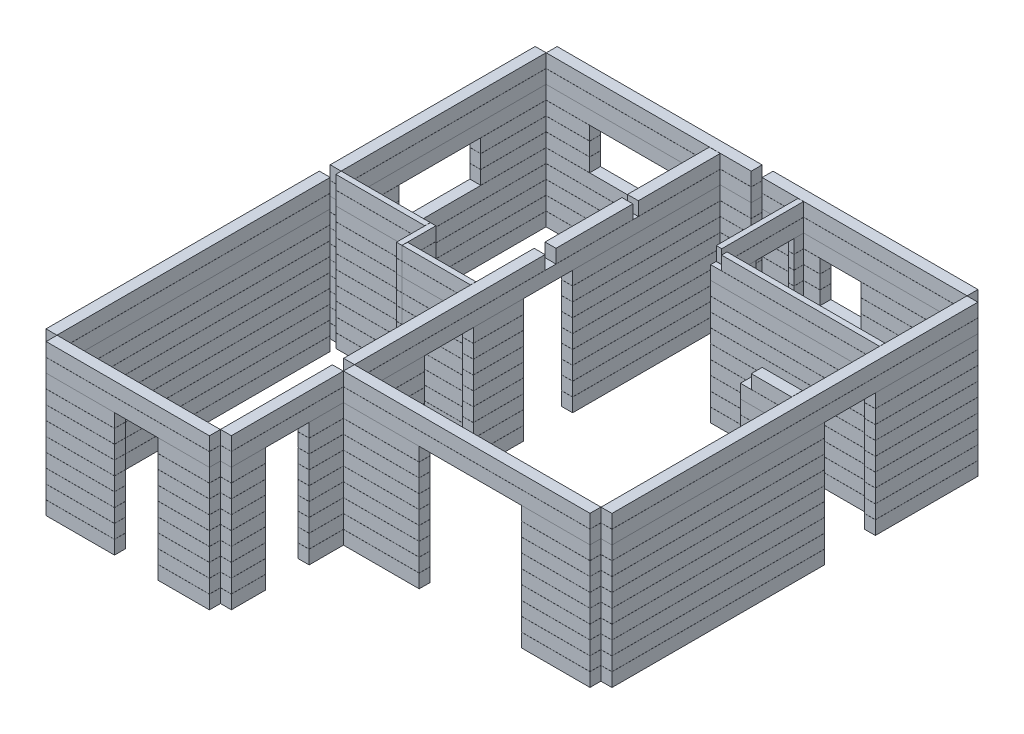
SolidWorks part; units mm, degrees
ref_plane "Спереди" through (0, 0, 0) normal (0, 0, 1) x (1, 0, 0)
ref_plane "Сверху" through (0, 0, 0) normal (0, 1, 0) x (1, 0, 0)
ref_plane "Справа" through (0, 0, 0) normal (1, 0, 0) x (0, 0, -1)
sketch "Эскиз1" plane through (0, 0, 0) normal (0, 1, 0) x (1, 0, 0)
  line L0 (8127, -7118) -> (3399, -7118) construction
  line L1 (0, 0) -> (8127, 0) construction
  line L2 (0, 0) -> (0, -9178) construction
  line L3 (0, -9378) -> (3399, -9378) construction
  line L4 (8127, 0) -> (8127, -7118) construction
  line L5 (3399, -7118) -> (3399, -9378) construction
  line L6 (7927, -203) -> (8127, -203)
  line L7 (203, 0) -> (3965, 0)
  line L8 (203, 0) -> (203, -200)
  line L9 (203, -200) -> (3965, -200)
  line L12 (0, -200) -> (0, -3962)
  line L14 (200, -200) -> (200, -3962)
  line L15 (203, -9378) -> (1457, -9378)
  line L16 (203, -9378) -> (203, -9178)
  line L17 (203, -9178) -> (1457, -9178)
  line L19 (3399, -9175) -> (3199, -9175)
  line L20 (3399, -9175) -> (3399, -8548)
  line L21 (3399, -7121) -> (3199, -7121)
  line L22 (3199, -9175) -> (3199, -8548)
  line L24 (8127, -203) -> (8127, -2084)
  line L26 (7927, -203) -> (7927, -2084)
  line L27 (7924, -7118) -> (6670, -7118)
  line L28 (7924, -7118) -> (7924, -6918)
  line L29 (7924, -6918) -> (6670, -6918)
  line L31 (1457, -9178) -> (1457, -9378)
  line L32 (2257, -9178) -> (2257, -9378)
  line L33 (2257, -9178) -> (3199, -9178)
  line L34 (2257, -9378) -> (3199, -9378)
  line L35 (4789, -6918) -> (4789, -7118)
  line L36 (6670, -6918) -> (6670, -7118)
  line L37 (4789, -6918) -> (3399, -6918)
  line L38 (4789, -7118) -> (3399, -7118)
  line L39 (7927, -2084) -> (8127, -2084)
  line L41 (7927, -3014) -> (8127, -3014)
  line L42 (7927, -3014) -> (7927, -6918)
  line L43 (8127, -3014) -> (8127, -6918)
  line L44 (4827, -376) -> (4927, -376)
  line L45 (3199, -203) -> (3399, -203)
  line L46 (3199, -203) -> (3199, -2912)
  line L47 (3199, -6915) -> (3399, -6915)
  line L48 (3399, -203) -> (3399, -2912)
  line L49 (1839, -3962) -> (1939, -3962)
  line L50 (1839, -3962) -> (1839, -4584)
  line L51 (1839, -4584) -> (1939, -4584)
  line L52 (1939, -3962) -> (1939, -4584)
  line L53 (203, -3962) -> (1836, -3962)
  line L54 (203, -3962) -> (203, -4062)
  line L55 (203, -4062) -> (1836, -4062)
  line L56 (1836, -3962) -> (1836, -4062)
  line L57 (1942, -4484) -> (3196, -4484)
  line L58 (1942, -4484) -> (1942, -4584)
  line L59 (1942, -4584) -> (3196, -4584)
  line L60 (3196, -4484) -> (3196, -4584)
  line L61 (4827, -1706) -> (7924, -1706)
  line L62 (4827, -1706) -> (4827, -1806)
  line L63 (4827, -1806) -> (7924, -1806)
  line L64 (7924, -1706) -> (7924, -1806)
  line L65 (4827, -203) -> (4927, -203)
  line L66 (4827, -203) -> (4827, -376)
  line L67 (4827, -1703) -> (4927, -1703)
  line L68 (4927, -203) -> (4927, -376)
  line L70 (4827, -1076) -> (4927, -1076)
  line L71 (4827, -1076) -> (4827, -1703)
  line L72 (4927, -1076) -> (4927, -1703)
  line L73 (3199, -7748) -> (3399, -7748)
  line L83 (3199, -8548) -> (3399, -8548)
  line L84 (3199, -7748) -> (3199, -7121)
  line L85 (3399, -7748) -> (3399, -7121)
  line L86 (3199, -4734) -> (3399, -4734)
  line L87 (6984, -3218) -> (7924, -3218)
  line L88 (6984, -3218) -> (6984, -3418)
  line L89 (6984, -3418) -> (7924, -3418)
  line L90 (7924, -3218) -> (7924, -3418)
  line L92 (3199, -5634) -> (3399, -5634)
  line L93 (3199, -5634) -> (3199, -6915)
  line L94 (3399, -5634) -> (3399, -6915)
  line L95 (3399, -2912) -> (3199, -2912)
  line L97 (3199, -3812) -> (3399, -3812)
  line L98 (3199, -3812) -> (3199, -4734)
  line L99 (3399, -3812) -> (3399, -4734)
  line L100 (200, -9178) -> (0, -9178)
  line L101 (3199, -9178) -> (3199, -9378)
  line L102 (3399, -6918) -> (3399, -7118)
  line L103 (7927, -6918) -> (8127, -6918)
  line L104 (0, -200) -> (200, -200)
  line L105 (0, -3962) -> (200, -3962)
  line L107 (0, -4162) -> (200, -4162)
  line L108 (0, -4162) -> (0, -9178)
  line L109 (200, -4162) -> (200, -9178)
  line L110 (7927, 0) -> (7927, -200)
  line L111 (3965, 0) -> (3965, -200)
  line L113 (4165, 0) -> (4165, -200)
  line L114 (4165, 0) -> (7927, 0)
  line L115 (4165, -200) -> (7927, -200)
  line L116 (0, -9378) -> (0, -9178) construction
  point P66 (4927, -1389.5)
  dimension "D1" = 8127
  dimension "D2" = 7118
  dimension "D3" = 9378
  dimension "D4" = 200
  dimension "D5" = 3
  dimension "D6" = 3
  dimension "D7" = 3
  dimension "D8" = 3762
  dimension "D9" = 200
  dimension "D10" = 3
  dimension "D11" = 3
  dimension "D12" = 3
  dimension "D13" = 2260
  dimension "D14" = 2999
  dimension "D15" = 2999
  dimension "D16" = 3762
  dimension "D17" = 5016
  dimension "D18" = 3762
  dimension "D19" = 4728
  dimension "D20" = 800
  dimension "D21" = 1254
  dimension "D22" = 1881
  dimension "D23" = 1254
  dimension "D24" = 930
  dimension "D25" = 1881
  dimension "D26" = 200
  dimension "D27" = 3
  dimension "D28" = 3
  dimension "D29" = 200
  dimension "D30" = 100
  dimension "D31" = 100
  dimension "D32" = 100
  dimension "D33" = 622
  dimension "D34" = 3
  dimension "D35" = 3
  dimension "D36" = 3
  dimension "D37" = 3
  dimension "D38" = 1633
  dimension "D39" = 1254
  dimension "D40" = 4594
  dimension "D41" = 3762
  dimension "D42" = 100
  dimension "D43" = 100
  dimension "D44" = 3
  dimension "D45" = 3
  dimension "D46" = 1500
  dimension "D47" = 3
  dimension "D48" = 700
  dimension "D49" = 627
  dimension "D50" = 173
  dimension "D51" = 3000
  dimension "D52" = 1428
  dimension "D53" = 942
  dimension "D54" = 1428
  dimension "D55" = 3500
  dimension "D60" = 800
  dimension "D61" = 627
  dimension "D62" = 200
  dimension "D63" = 940
  dimension "D64" = 3
  dimension "D65" = 3500
  dimension "D66" = 4528
  dimension "D67" = 5112
  dimension "D68" = 900
  dimension "D69" = 150
  dimension "D70" = 900
  dimension "D72" = 200
  dimension "D73" = 200
  dimension "D74" = 200
extrude "Бобышка-Вытянуть3" add sketch "Эскиз1" along normal blind 250 contours L90 L87 L88 L89 | L42 L103 L43 L41 | L26 L39 L24 L6 | L113 L115 L110 L114 | L61 L64 L63 L62 | L71 L67 L72 L70 | L66 L44 L68 L65 | L27 L36 L29 L28 | L8 L9 L111 L7 | L45 L48 L95 L46 | L14 L105 L12 L104 | L58 L57 L60 L59 | L86 L99 L97 L98 | L54 L53 L56 L55 | L50 L49 L52 L51 | L100 L108 L107 L109 | L47 L94 L92 L93 | L35 L38 L102 L37 | L21 L84 L73 L85 | L19 L22 L83 L20 | L32 L34 L101 L33 | L15 L31 L17 L16 region at (8027, 0, 1143.5) region at (8027, 0, 4966) region at (7454, 0, 3318) region at (6046, 0, 100)
pattern_linear "Линейный массив1" count 9 spacing 252 along (0, 1, 0) of "Бобышка-Вытянуть3"
sketch "Эскиз2" plane through (0, 0, 0) normal (-1, 0, 0) x (0, 0, 1)
  line L0 (200, 1260) -> (3962, 1260) construction
  line L1 (200, 2014) -> (3962, 2014) construction
  line L2 (1399.6584, 1260) -> (2899.6584, 1260)
  line L3 (1399.6584, 1260) -> (1399.6584, 2014)
  line L4 (1399.6584, 2014) -> (2899.6584, 2014)
  line L5 (2899.6584, 1260) -> (2899.6584, 2014)
  dimension "D1" = 1500
extrude "Вырез-Вытянуть2" cut sketch "Эскиз2" against normal blind 250
sketch "Эскиз3" plane through (0, 0, 0) normal (0, 0, -1) x (-1, 0, 0)
  line L0 (-203, 2014) -> (-3965, 2014) construction
  line L1 (-2500, 2014) -> (-1000, 2014)
  line L2 (-2500, 2014) -> (-2500, 1260)
  line L3 (-2500, 1260) -> (-1000, 1260)
  line L4 (-1000, 2014) -> (-1000, 1260)
  line L5 (-203, 1260) -> (-3965, 1260) construction
  line L6 (0, 1762) -> (0, 1512) construction
  line L7 (-4165, 2014) -> (-7927, 2014) construction
  line L8 (-5977, 2014) -> (-5227, 2014)
  line L9 (-5977, 2014) -> (-5977, 1260)
  line L10 (-5977, 1260) -> (-5227, 1260)
  line L11 (-5227, 2014) -> (-5227, 1260)
  line L12 (-4165, 1260) -> (-7927, 1260) construction
  line L13 (-4927, 2014) -> (-4927, 1764) construction
  dimension "D1" = 1500
  dimension "D2" = 1000
  dimension "D3" = 750
  dimension "D4" = 300
extrude "Вырез-Вытянуть3" cut sketch "Эскиз3" against normal blind 593
sketch "Эскиз4" plane through (0, 2266, 0) normal (0, 1, 0) x (1, 0, 0)
  line L0 (203, -200) -> (3965, -200) construction
  line L1 (203, 0) -> (3965, 0)
  line L2 (203, 0) -> (203, -200)
  line L3 (203, -200) -> (3965, -200)
  line L4 (3965, 0) -> (3965, -200)
  line L5 (3199, -203) -> (3399, -203) construction
  line L6 (4165, -200) -> (7927, -200)
  line L7 (4165, -200) -> (4165, 0)
  line L8 (4165, 0) -> (7927, 0)
  line L9 (7927, -200) -> (7927, 0)
  line L10 (4827, -203) -> (4927, -203)
  line L11 (4827, -203) -> (4827, -1703)
  line L12 (4827, -1703) -> (4927, -1703)
  line L13 (4927, -203) -> (4927, -1703)
  line L14 (4827, -1806) -> (7924, -1806)
  line L15 (4827, -1806) -> (4827, -1706)
  line L16 (4827, -1706) -> (7924, -1706)
  line L17 (7924, -1806) -> (7924, -1706)
  line L18 (8127, -203) -> (7927, -203)
  line L19 (8127, -203) -> (8127, -6918)
  line L20 (8127, -6918) -> (7927, -6918)
  line L21 (7927, -203) -> (7927, -6918)
  line L22 (6984, -3218) -> (7924, -3218)
  line L23 (6984, -3218) -> (6984, -3418)
  line L24 (6984, -3418) -> (7924, -3418)
  line L25 (7924, -3218) -> (7924, -3418)
  line L26 (3399, -6915) -> (3199, -6915)
  line L27 (3399, -6915) -> (3399, -203)
  line L28 (3399, -203) -> (3199, -203)
  line L29 (3199, -6915) -> (3199, -203)
  line L34 (3199, -203) -> (3199, -2912) construction
  line L35 (3199, -5634) -> (3199, -6915) construction
  line L36 (3199, -6915) -> (3399, -6915) construction
  line L38 (3399, -7118) -> (7924, -7118)
  line L39 (3399, -7118) -> (3399, -6918)
  line L40 (3399, -6918) -> (7924, -6918)
  line L41 (7924, -7118) -> (7924, -6918)
  line L42 (3199, -7121) -> (3399, -7121)
  line L43 (3199, -7121) -> (3199, -9175)
  line L44 (3199, -9175) -> (3399, -9175)
  line L45 (3399, -7121) -> (3399, -9175)
  line L46 (3199, -9378) -> (203, -9378)
  line L47 (3199, -9378) -> (3199, -9178)
  line L48 (3199, -9178) -> (203, -9178)
  line L49 (203, -9378) -> (203, -9178)
  line L50 (0, -9178) -> (200, -9178)
  line L51 (0, -9178) -> (0, -4162)
  line L52 (0, -4162) -> (200, -4162)
  line L53 (200, -9178) -> (200, -4162)
  line L54 (0, -3962) -> (200, -3962)
  line L55 (0, -3962) -> (0, -200)
  line L56 (0, -200) -> (200, -200)
  line L57 (200, -3962) -> (200, -200)
  line L58 (203, -4062) -> (1836, -4062)
  line L59 (203, -4062) -> (203, -3962)
  line L60 (203, -3962) -> (1836, -3962)
  line L61 (1836, -4062) -> (1836, -3962)
  line L62 (1939, -3962) -> (1839, -3962)
  line L63 (1939, -3962) -> (1939, -4584)
  line L64 (1939, -4584) -> (1839, -4584)
  line L65 (1839, -3962) -> (1839, -4584)
  line L66 (1942, -4484) -> (3196, -4484)
  line L67 (1942, -4484) -> (1942, -4584)
  line L68 (1942, -4584) -> (3196, -4584)
  line L69 (3196, -4484) -> (3196, -4584)
extrude "Бобышка-Вытянуть4" add sketch "Эскиз4" along normal blind 250 separate body
extrude "Бобышка-Вытянуть5" add sketch "Эскиз4<2>" along normal blind 250 from offset 252 separate body
sketch "Эскиз4<2>" plane through (0, 2266, 0) normal (0, 1, 0) x (1, 0, 0) same geometry as "Эскиз4"
sketch "Эскиз5" plane through (0, 2768, 0) normal (0, 1, 0) x (1, 0, 0)
  line L0 (7924, -3218) -> (6984, -3218) construction
  line L1 (7184, -3218) -> (3199, -3218)
  line L2 (7184, -3218) -> (7184, -3418)
  line L3 (7184, -3418) -> (3199, -3418)
  line L4 (3199, -3218) -> (3199, -3418)
  line L5 (3199, -203) -> (3199, -6915) construction
  line L6 (6984, -3418) -> (7924, -3418) construction
  line L7 (6984, -3218) -> (6984, -3418) construction
  line L8 (7924, -1706) -> (4827, -1706) construction
  line L9 (5027, -1706) -> (3199, -1706)
  line L10 (5027, -1706) -> (5027, -1806)
  line L11 (5027, -1806) -> (3199, -1806)
  line L12 (3199, -1706) -> (3199, -1806)
  line L13 (4827, -1806) -> (7924, -1806) construction
  line L14 (4827, -1706) -> (4827, -1806) construction
  point P18 (0, 0)
  dimension "D1" = 200
  dimension "D2" = 200
extrude "Вырез-Вытянуть4" cut sketch "Эскиз5" against normal blind 250
